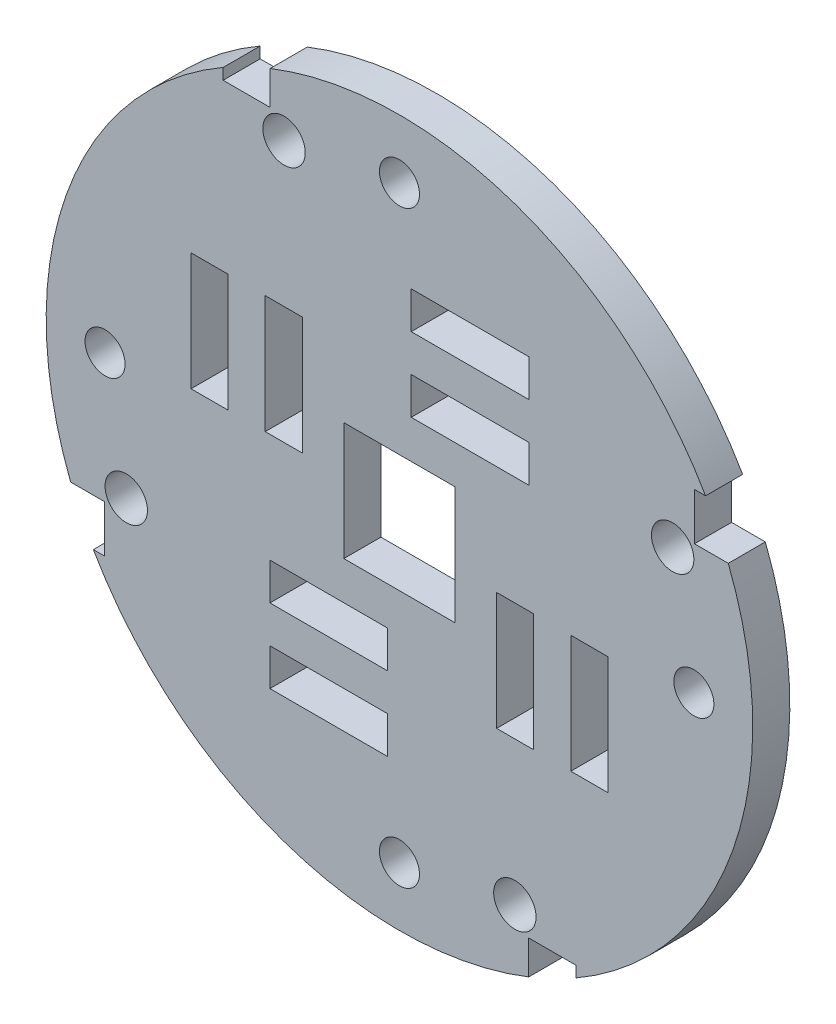
SolidWorks part; units mm, degrees
material "Hexcel AS4C (3000 Filaments)"
ref_plane "Front Plane" through (0, 0, 0) normal (0, 0, 1) x (1, 0, 0)
ref_plane "Top Plane" through (0, 0, 0) normal (0, 1, 0) x (1, 0, 0)
ref_plane "Right Plane" through (0, 0, 0) normal (1, 0, 0) x (0, 0, -1)
sketch "Sketch1" plane through (0, 0, 0) normal (0, 0, 1) x (1, 0, 0)
  circle A0 centre (0, 0) radius 38.1
  dimension "D1" = 76.2
extrude "Boss-Extrude1" add sketch "Sketch1" along normal blind 4 contours A0
sketch "Sketch2" plane through (0, 0, 4) normal (0, 0, 1) x (1, 0, 0)
  line L0 (-1.27, -10.478) -> (-13.97, -10.478)
  line L1 (10.478, -1.27) -> (14.478, -1.27)
  line L2 (10.478, -1.27) -> (10.478, -13.97)
  line L3 (10.478, -13.97) -> (14.478, -13.97)
  line L4 (14.478, -1.27) -> (14.478, -13.97)
  line L5 (18.478, -1.27) -> (22.478, -1.27)
  line L6 (18.478, -1.27) -> (18.478, -13.97)
  line L7 (18.478, -13.97) -> (22.478, -13.97)
  line L8 (22.478, -1.27) -> (22.478, -13.97)
  line L9 (-1.27, -10.478) -> (-1.27, -14.478)
  line L10 (-1.27, -14.478) -> (-13.97, -14.478)
  line L11 (-13.97, -10.478) -> (-13.97, -14.478)
  line L12 (-1.27, -18.478) -> (-13.97, -18.478)
  line L13 (-1.27, -18.478) -> (-1.27, -22.478)
  line L14 (-1.27, -22.478) -> (-13.97, -22.478)
  line L15 (-13.97, -18.478) -> (-13.97, -22.478)
  line L16 (-10.478, 1.27) -> (-10.478, 13.97)
  line L17 (-10.478, 1.27) -> (-14.478, 1.27)
  line L18 (-14.478, 1.27) -> (-14.478, 13.97)
  line L19 (-10.478, 13.97) -> (-14.478, 13.97)
  line L20 (-18.478, 1.27) -> (-18.478, 13.97)
  line L21 (-18.478, 1.27) -> (-22.478, 1.27)
  line L22 (-22.478, 1.27) -> (-22.478, 13.97)
  line L23 (-18.478, 13.97) -> (-22.478, 13.97)
  line L24 (1.27, 10.478) -> (13.97, 10.478)
  line L25 (1.27, 10.478) -> (1.27, 14.478)
  line L26 (1.27, 14.478) -> (13.97, 14.478)
  line L27 (13.97, 10.478) -> (13.97, 14.478)
  line L28 (1.27, 18.478) -> (13.97, 18.478)
  line L29 (1.27, 18.478) -> (1.27, 22.478)
  line L30 (1.27, 22.478) -> (13.97, 22.478)
  line L31 (13.97, 18.478) -> (13.97, 22.478)
  circle A0 centre (12.446, -29.464) radius 2.286
  circle A1 centre (-29.464, -12.446) radius 2.286
  circle A2 centre (-12.446, 29.464) radius 2.286
  circle A3 centre (29.464, 12.446) radius 2.286
  point P12 (14.478, -7.62)
  point P37 (0, 0)
  point P45 (0, 0)
  dimension "D8" = 4.572
  dimension "D1" = 4
  dimension "D2" = 4
  dimension "D3" = 4
  dimension "D4" = 12.7
  dimension "D5" = 14.478
  dimension "D6" = 1.27
  dimension "D9" = 21.844
  dimension "D11" = 2.032
  dimension "D7" = 4
  dimension "D10" = 4
extrude "Cut-Extrude1" cut sketch "Sketch2" against normal through all
sketch "Sketch3" plane through (0, 0, 4) normal (0, 0, 1) x (1, 0, 0)
  line L1 (-6, -6.35) -> (6, -6.35)
  line L2 (-6, -6.35) -> (-6, 6.35)
  line L3 (-6, 6.35) -> (6, 6.35)
  line L4 (6, -6.35) -> (6, 6.35)
  line L5 (-6, -6.35) -> (6, 6.35) construction
  line L6 (-6, 6.35) -> (6, -6.35) construction
  point P0 (0, 0)
  dimension "D1" = 12
  dimension "D2" = 12.7
extrude "Cut-Extrude2" cut sketch "Sketch3" against normal up to next
sketch "Sketch4" plane through (0, 0, 4) normal (0, 0, 1) x (1, 0, 0)
  circle A0 centre (0, -31.75) radius 2.159
  circle A1 centre (31.75, 0) radius 2.159
  circle A2 centre (0, 31.75) radius 2.159
  circle A3 centre (-31.75, 0) radius 2.159
  point P9 (0, 0)
  dimension "D1" = 4.318
  dimension "D2" = 31.75
  dimension "D3" = 4
extrude "Cut-Extrude3" cut sketch "Sketch4" against normal through all
sketch "Sketch5" plane through (0, 0, 4) normal (0, 0, 1) x (1, 0, 0)
  line L0 (13.97, 18.478) -> (13.97, 14.478) construction
  line L1 (31.8124, 13.938) -> (36.8924, 13.938)
  line L2 (31.8124, 13.938) -> (31.8124, 19.018)
  line L3 (31.8124, 19.018) -> (36.8924, 19.018)
  line L4 (36.8924, 13.938) -> (36.8924, 19.018)
  line L5 (31.8124, 13.938) -> (36.8924, 19.018) construction
  line L6 (31.8124, 19.018) -> (36.8924, 13.938) construction
  line L7 (13.938, -31.8124) -> (19.018, -31.8124)
  line L8 (13.938, -31.8124) -> (13.938, -36.8924)
  line L9 (13.938, -36.8924) -> (19.018, -36.8924)
  line L10 (19.018, -31.8124) -> (19.018, -36.8924)
  line L11 (-31.8124, -13.938) -> (-31.8124, -19.018)
  line L12 (-31.8124, -13.938) -> (-36.8924, -13.938)
  line L13 (-36.8924, -13.938) -> (-36.8924, -19.018)
  line L14 (-31.8124, -19.018) -> (-36.8924, -19.018)
  line L15 (-13.938, 31.8124) -> (-19.018, 31.8124)
  line L16 (-13.938, 31.8124) -> (-13.938, 36.8924)
  line L17 (-13.938, 36.8924) -> (-19.018, 36.8924)
  line L18 (-19.018, 31.8124) -> (-19.018, 36.8924)
  circle A0 centre (0, 0) radius 38.1 construction
  point P0 (34.3524, 16.478)
  point P12 (13.97, 16.478)
  point P27 (0, 0)
  dimension "D1" = 5.08
  dimension "D2" = 5.08
  dimension "D3" = 4
extrude "Cut-Extrude4" cut sketch "Sketch5" against normal up to next
